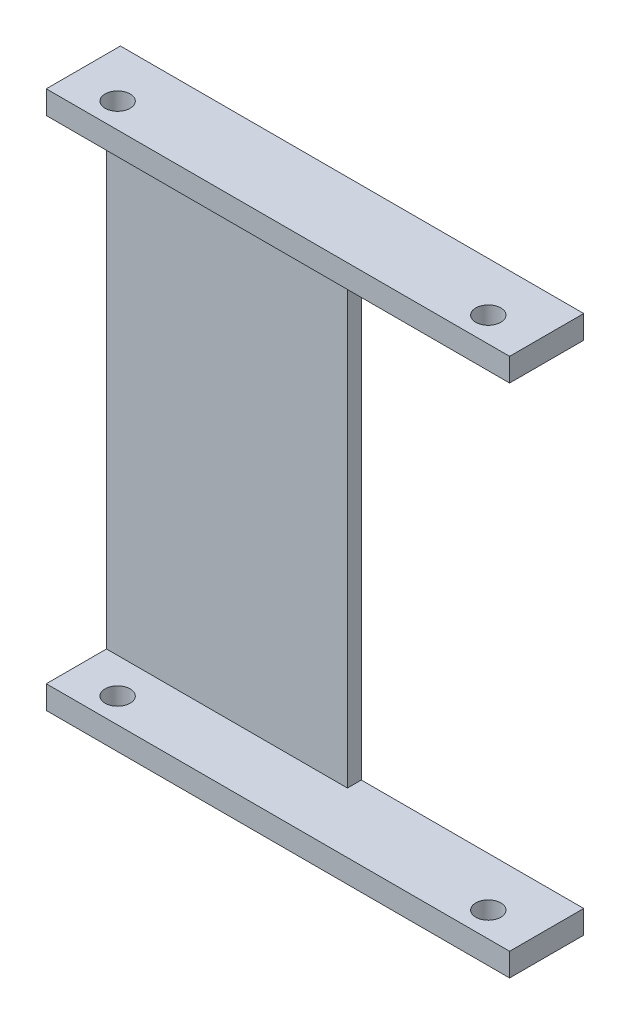
SolidWorks part; units mm, degrees
ref_plane "Front Plane" through (0, 0, 0) normal (0, 0, 1) x (1, 0, 0)
ref_plane "Top Plane" through (0, 0, 0) normal (0, 1, 0) x (1, 0, 0)
ref_plane "Right Plane" through (0, 0, 0) normal (1, 0, 0) x (0, 0, -1)
sketch "Sketch1" plane through (0, 0, 0) normal (0, 0, 1) x (1, 0, 0)
  line L1 (0, 0) -> (127, 0)
  line L2 (0, 0) -> (0, 147.574)
  line L3 (0, 147.574) -> (127, 147.574)
  line L4 (127, 0) -> (127, 147.574)
  dimension "D1" = 127
  dimension "D2" = 147.574
extrude "Boss-Extrude1" add sketch "Sketch1" along normal blind 3.81
sketch "Sketch3" plane through (0, 0, 3.81) normal (0, 0, 1) x (1, 0, 0)
  line L0 (127, 0) -> (127, 147.574) construction
  line L1 (0, 147.574) -> (127, 147.574)
  line L2 (0, 147.574) -> (0, 141.224)
  line L3 (0, 141.224) -> (127, 141.224)
  line L4 (127, 147.574) -> (127, 141.224)
  line L6 (0, 0) -> (127, 0)
  line L7 (0, 0) -> (0, 6.35)
  line L8 (0, 6.35) -> (127, 6.35)
  line L9 (127, 0) -> (127, 6.35)
  dimension "D1" = 6.35
  dimension "D2" = 6.35
extrude "Boss-Extrude2" add sketch "Sketch3" along normal blind 16.51
sketch "Sketch4" plane through (0, 0, 0) normal (0, -1, 0) x (1, 0, 0)
  line L0 (0, 20.32) -> (127, 20.32) construction
  line L1 (127, 20.32) -> (127, 0) construction
  circle A0 centre (12.7, 13.462) radius 3.429
  circle A1 centre (114.3, 13.462) radius 3.429
  dimension "D2" = 6.858
  dimension "D3" = 6.858
  dimension "D4" = 6.858
  dimension "D6" = 6.858
  dimension "D1" = 101.6
  dimension "D5" = 12.7
extrude "Cut-Extrude1" cut sketch "Sketch4" against normal through all
sketch "Sketch7" plane through (0, 0, 3.81) normal (0, 0, 1) x (1, 0, 0)
  line L0 (127, 73.787) -> (66.04, 73.787) construction
  line L1 (127, 6.35) -> (127, 141.224) construction
  line L2 (66.04, 141.224) -> (66.04, 6.35) construction
  line L3 (0, 141.224) -> (127, 141.224) construction
  line L4 (127, 6.35) -> (0, 6.35) construction
  line L6 (127, 141.224) -> (66.04, 141.224)
  line L7 (127, 141.224) -> (127, 6.35)
  line L8 (127, 6.35) -> (66.04, 6.35)
  line L9 (66.04, 141.224) -> (66.04, 6.35)
  dimension "D1" = 60.96
extrude "Cut-Extrude3" cut sketch "Sketch7" against normal up to surface (3.81 mm away) contours L7 L6 L9 L8 up to face at (63.5, 73.787, 0)
